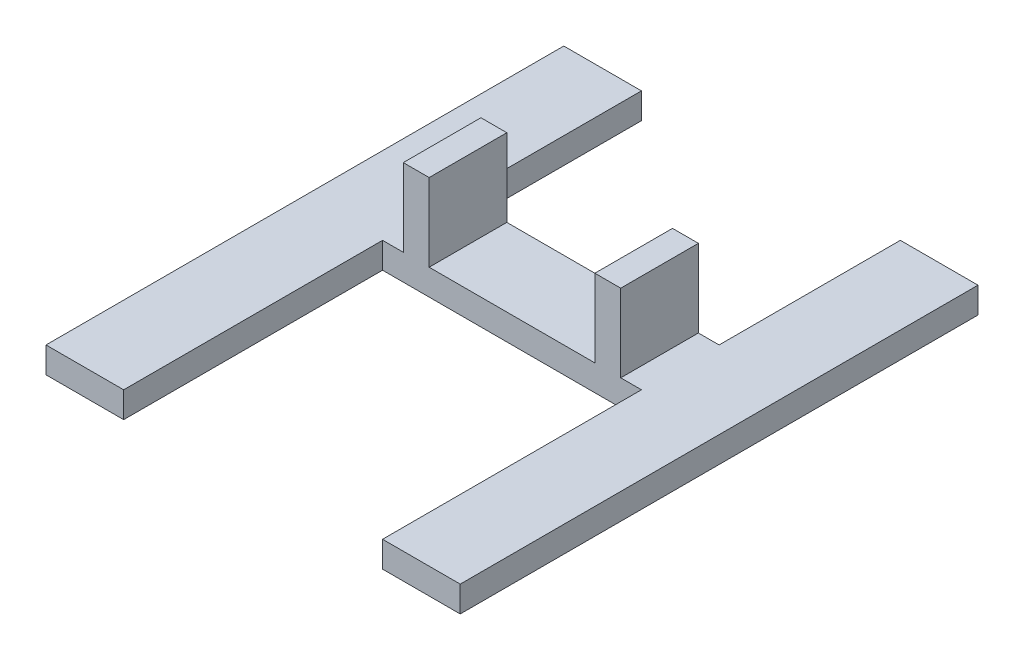
SolidWorks part; units mm, degrees
ref_plane "Front Plane" through (0, 0, 0) normal (0, 0, 1) x (1, 0, 0)
ref_plane "Top Plane" through (0, 0, 0) normal (0, 1, 0) x (1, 0, 0)
ref_plane "Right Plane" through (0, 0, 0) normal (1, 0, 0) x (0, 0, -1)
sketch "Sketch1" plane through (0, 0, 0) normal (0, 1, 0) x (1, 0, 0)
  line L0 (0, 0) -> (0, 100)
  line L1 (0, 100) -> (15, 100)
  line L2 (15, 100) -> (15, 0)
  line L3 (15, 0) -> (0, 0)
  line L4 (65, 100) -> (65, 0)
  line L5 (65, 0) -> (80, 0)
  line L6 (80, 0) -> (80, 100)
  line L7 (80, 100) -> (65, 100)
  line L8 (15, 50) -> (65, 50)
  line L9 (15, 65) -> (65, 65)
  line L10 (15, 65) -> (15, 50)
  line L11 (65, 65) -> (65, 50)
  dimension "D1" = 15
  dimension "D2" = 100
  dimension "D3" = 80
  dimension "D4" = 15
extrude "Boss-Extrude1" add sketch "Sketch1" along normal mid plane 5 contours L3 L2 L1 L0 | L9 L2 L8 L4 | L6 L7 L4 L5 region at (7.5, 0, -50) region at (40, 0, -57.5) region at (72.5, 0, -50)
sketch "Sketch2" plane through (0, 2.5, 0) normal (0, 1, 0) x (1, 0, 0)
  line L0 (40, 65) -> (40, 50) construction
  line L1 (15, 65) -> (65, 65) construction
  line L2 (15, 50) -> (65, 50) construction
  line L3 (56, 65) -> (56, 50)
  line L4 (56, 50) -> (61, 50)
  line L5 (61, 50) -> (61, 65)
  line L6 (61, 65) -> (56, 65)
  line L7 (19, 65) -> (19, 50)
  line L8 (19, 50) -> (24, 50)
  line L9 (24, 50) -> (24, 65)
  line L10 (24, 65) -> (19, 65)
  line L11 (24, 65) -> (56, 65) construction
  point P12 (40, 65)
  dimension "D1" = 5
  dimension "D2" = 32
extrude "Boss-Extrude2" add sketch "Sketch2" along normal blind 15
